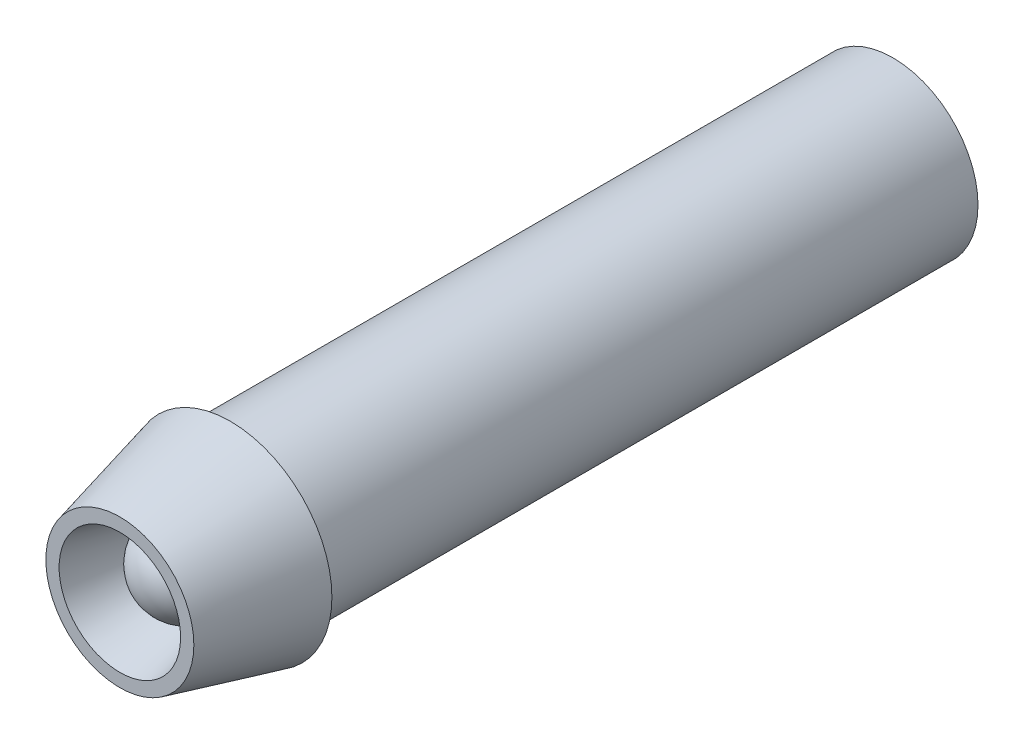
SolidWorks part; units mm, degrees
ref_plane "Plan de face" through (0, 0, 0) normal (0, 0, 1) x (1, 0, 0)
ref_plane "Plan de dessus" through (0, 0, 0) normal (0, 1, 0) x (1, 0, 0)
ref_plane "Plan de droite" through (0, 0, 0) normal (1, 0, 0) x (0, 0, -1)
sketch "Esquisse1" plane through (0, 0, 0) normal (0, 0, 1) x (1, 0, 0)
  circle A0 centre (0, 0) radius 2
  circle A1 centre (0, 0) radius 4.85
  dimension "D1" = 4
  dimension "D2" = 9.7
extrude "Boss.-Extru.1" add sketch "Esquisse1" along normal blind 5
chamfer "Chanfrein1" distance 6 distance2 1.5 1 edges at (4.85, 0, 5) first distance on face at (4.85, 0, 5)
chamfer "Chanfrein2" distance 0.75 distance2 3 1 edges at (2, 0, 5) first distance on face at (3.35, 0, 5)
ref_plane "Plan2" through (0, 0, 2) normal (0, 0, 1) x (1, 0, 0)
sketch "Esquisse4" plane through (0, 0, 2) normal (0, 0, 1) x (1, 0, 0)
  circle A0 centre (0, 0) radius 2
extrude "Boss.-Extru.2" add sketch "Esquisse4" along normal blind 2 separate body
fillet "Congé1" radius 2 1 edges at (2, 0, 4)
sketch "Esquisse5" plane through (0, 0, 0) normal (0, 0, -1) x (-1, 0, 0)
  circle A0 centre (0, 0) radius 3.85
  dimension "D1" = 7.7
extrude "Boss.-Extru.3" add sketch "Esquisse5" along normal blind 30
